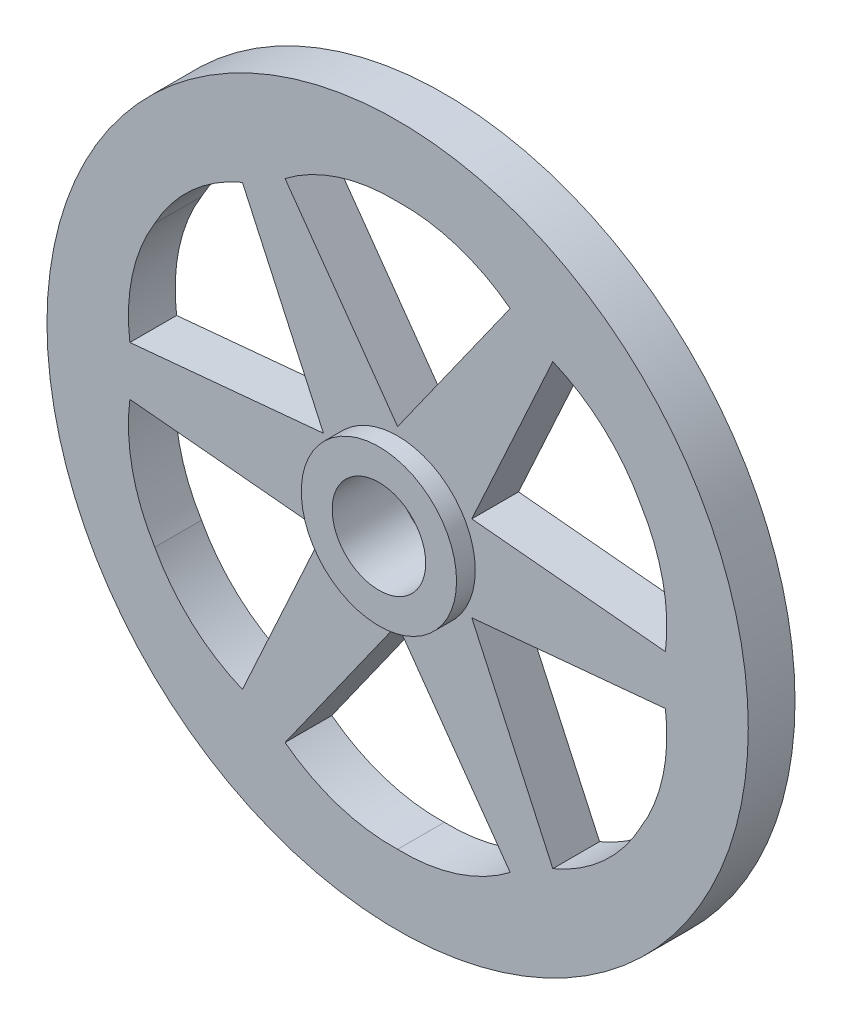
SolidWorks part; units mm, degrees
ref_plane "Front Plane" through (0, 0, 0) normal (0, 0, 1) x (1, 0, 0)
ref_plane "Top Plane" through (0, 0, 0) normal (0, 1, 0) x (1, 0, 0)
ref_plane "Right Plane" through (0, 0, 0) normal (1, 0, 0) x (0, 0, -1)
sketch "Sketch1" plane through (0, 0, 0) normal (0, 0, 1) x (1, 0, 0)
  circle A0 centre (0, 0) radius 37.5
  circle A1 centre (0, 0) radius 5
  dimension "D1" = 75
  dimension "D2" = 10
extrude "Boss-Extrude1" add sketch "Sketch1" along normal mid plane 5
sketch "Sketch2" plane through (0, 0, 0) normal (0, 0, 1) x (1, 0, 0)
  line L0 (0, 0) -> (0, 32.5712) construction
  line L1 (0, 9.1586) -> (-12.0371, 26.1152)
  line L2 (0, 9.1586) -> (12.0371, 26.1152)
  arc A0 (-12.0371, 26.1152) -> (0, 29.9881) centre (-0.5568, 11.0765) cw
  arc A1 (12.0371, 26.1152) -> (0, 29.9881) centre (0.5568, 11.0765) ccw
  point P9 (-8.6876, 27.0572)
  point P10 (-0.5568, 9.1586)
  point P11 (-12.0371, 26.1152)
extrude "Cut-Extrude1" cut sketch "Sketch2" along normal mid plane 8
pattern_circular "CirPattern1" count 6 over 360 about axis through (0, 0, 2.5) along (0, 0, -1) of "Cut-Extrude1" reverse direction yes
sketch "Sketch4" plane through (0, 0, 2.5) normal (0, 0, 1) x (1, 0, 0)
  circle A0 centre (0, 0) radius 8.3027
  circle A1 centre (0, 0) radius 5
extrude "Boss-Extrude2" add sketch "Sketch4" along normal blind 2
